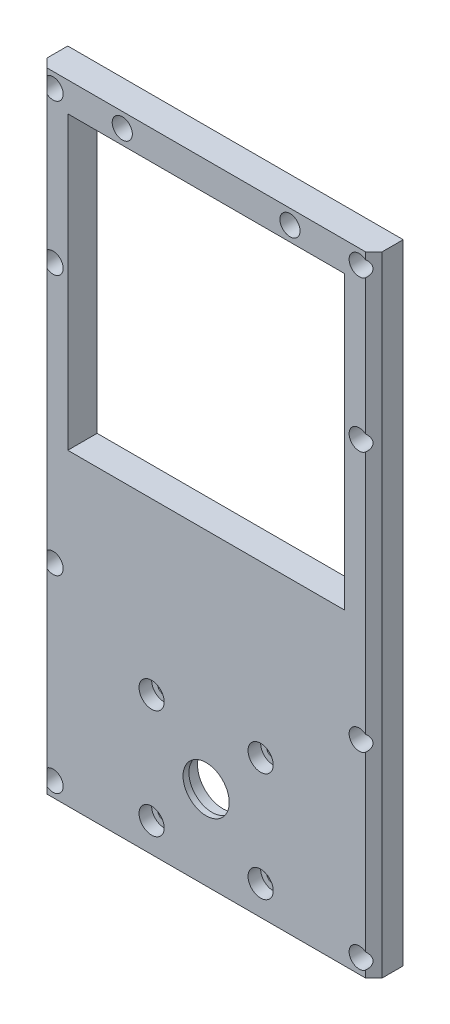
SolidWorks part; units mm, degrees
ref_plane "Front Plane" through (0, 0, 0) normal (0, 0, 1) x (1, 0, 0)
ref_plane "Top Plane" through (0, 0, 0) normal (0, 1, 0) x (1, 0, 0)
ref_plane "Right Plane" through (0, 0, 0) normal (1, 0, 0) x (0, 0, -1)
sketch "Sketch1" plane through (0, 0, 0) normal (0, 0, 1) x (1, 0, 0)
  line L1 (-40, -75) -> (40, -75)
  line L2 (-40, -75) -> (-40, 75)
  line L3 (-40, 75) -> (40, 75)
  line L4 (40, -75) -> (40, 75)
  line L5 (-40, -75) -> (40, 75) construction
  line L6 (-40, 75) -> (40, -75) construction
  line L7 (-33, -68) -> (33, -68)
  line L8 (-33, -68) -> (-33, 68)
  line L9 (-33, 68) -> (33, 68)
  line L10 (33, -68) -> (33, 68)
  line L11 (-33, -68) -> (33, 68) construction
  line L12 (-33, 68) -> (33, -68) construction
  point P0 (0, 0)
  point P6 (0, 0)
  dimension "D1" = 150
  dimension "D2" = 80
  dimension "D3" = 7
  dimension "D4" = 7
extrude "Boss-Extrude1" add sketch "Sketch1" along normal blind 7
sketch "Sketch2" plane through (0, 0, 7) normal (0, 0, 1) x (1, 0, 0)
  line L0 (33, -68) -> (33, 68) construction
  line L1 (-33, -68) -> (33, -68)
  line L2 (-33, -68) -> (-33, -32)
  line L3 (-33, -32) -> (33, -32)
  line L4 (33, -68) -> (33, -32)
  dimension "D1" = 36
extrude "Boss-Extrude2" add sketch "Sketch2" against normal up to surface (7 mm away) up to face at (0, 0, 0)
sketch "Sketch3" plane through (0, 0, 0) normal (0, 0, -1) x (-1, 0, 0)
  line L0 (0, -75) -> (0, -55) construction
  line L1 (40, -75) -> (-40, -75) construction
  circle A0 centre (0, -55) radius 5.5
  dimension "D1" = 11
  dimension "D2" = 20
extrude "Cut-Extrude1" cut sketch "Sketch3" against normal through all
sketch "Sketch4" plane through (0, 0, 0) normal (0, 0, -1) x (-1, 0, 0)
  circle A0 centre (0, -55) radius 6.05
  dimension "D1" = 12.1
extrude "Cut-Extrude2" cut sketch "Sketch4" against normal offset from surface (5.6 mm away) 1.4 up to face at (-5.5, -55, 7)
sketch "Sketch5" plane through (0, 0, 0) normal (0, 0, -1) x (-1, 0, 0)
  circle A0 centre (0, -55) radius 11
  dimension "D1" = 22
extrude "Cut-Extrude3" cut sketch "Sketch5" against normal offset from surface (3 mm away) 2.6 up to face at (-6.05, -55, 5.6)
sketch "Sketch6" plane through (0, 0, 0) normal (0, 0, -1) x (-1, 0, 0)
  line L1 (-13, -68) -> (13, -68) construction
  line L2 (-13, -68) -> (-13, -42) construction
  line L3 (-13, -42) -> (13, -42) construction
  line L4 (13, -68) -> (13, -42) construction
  line L5 (-13, -68) -> (13, -42) construction
  line L6 (-13, -42) -> (13, -68) construction
  circle A0 centre (-13, -42) radius 1.6
  circle A1 centre (13, -42) radius 1.6
  circle A2 centre (13, -68) radius 1.6
  circle A3 centre (-13, -68) radius 1.6
  point P0 (0, -55)
  dimension "D2" = 3.2
  dimension "D1" = 26
extrude "Cut-Extrude4" cut sketch "Sketch6" against normal through all
sketch "Sketch7" plane through (0, 0, 0) normal (0, 0, -1) x (-1, 0, 0)
  line L1 (-25, -74) -> (25, -74)
  line L2 (-25, -74) -> (-25, -36)
  line L3 (-25, -36) -> (25, -36)
  line L4 (25, -74) -> (25, -36)
  line L5 (-25, -74) -> (25, -36) construction
  line L6 (-25, -36) -> (25, -74) construction
  point P0 (0, -55)
  dimension "D1" = 50
  dimension "D2" = 38
extrude "Cut-Extrude5" cut sketch "Sketch7" against normal blind 1
sketch "Sketch8" plane through (0, 0, 7) normal (0, 0, 1) x (1, 0, 0)
  circle A0 centre (-13, -42) radius 3
  circle A1 centre (13, -42) radius 3
  circle A2 centre (13, -68) radius 3
  circle A3 centre (-13, -68) radius 3
  dimension "D1" = 6
extrude "Cut-Extrude6" cut sketch "Sketch8" against normal blind 3
sketch "Sketch9" plane through (0, 0, 7) normal (0, 0, 1) x (1, 0, 0)
  line L0 (-40, 75) -> (-40, -75) construction
  line L1 (-36.5, -71.5) -> (36.5, -71.5) construction
  line L2 (-36.5, -71.5) -> (-36.5, 71.5) construction
  line L3 (-36.5, 71.5) -> (36.5, 71.5) construction
  line L4 (36.5, -71.5) -> (36.5, 71.5) construction
  line L5 (-36.5, -71.5) -> (36.5, 71.5) construction
  line L6 (-36.5, 71.5) -> (36.5, -71.5) construction
  line L7 (40, 75) -> (-40, 75) construction
  circle A0 centre (-36.5, 71.5) radius 1.35
  circle A1 centre (36.5, 71.5) radius 1.35
  circle A4 centre (-36.5, -71.5) radius 1.35
  circle A5 centre (36.5, -71.5) radius 1.35
  circle A6 centre (-36.5, 35.5) radius 1.35
  circle A7 centre (36.5, 35.5) radius 1.35
  circle A8 centre (36.5, -26.5) radius 1.35
  circle A9 centre (-36.5, -26.5) radius 1.35
  point P0 (0, 0)
  dimension "D3" = 2.7
  dimension "D1" = 3.5
  dimension "D2" = 3.5
  dimension "D4" = 45
  dimension "D5" = 36
extrude "Cut-Extrude7" cut sketch "Sketch9" against normal through all
sketch "Sketch10" plane through (0, 0, 7) normal (0, 0, 1) x (1, 0, 0)
  circle A0 centre (-36.5, 71.5) radius 2.4
  circle A1 centre (36.5, 35.5) radius 2.4
  circle A2 centre (-36.5, 35.5) radius 2.4
  circle A3 centre (36.5, 71.5) radius 2.4
  circle A4 centre (-36.5, -71.5) radius 2.4
  circle A5 centre (36.5, -71.5) radius 2.4
  circle A6 centre (-36.5, -26.5) radius 2.4
  circle A7 centre (36.5, -26.5) radius 2.4
  dimension "D1" = 4.8
extrude "Cut-Extrude8" cut sketch "Sketch10" against normal blind 5
chamfer "Chamfer1" distance 2 angle 45 2 edges at (-40, 0, 7) (40, 0, 7)
sketch "Sketch11" plane through (0, 0, 7) normal (0, 0, 1) x (1, 0, 0)
  line L0 (33, -32) -> (33, 68) construction
  line L1 (-33, -32) -> (33, -32)
  line L2 (-33, -32) -> (-33, -1.5)
  line L3 (-33, -1.5) -> (33, -1.5)
  line L4 (33, -32) -> (33, -1.5)
  line L5 (-38, -75) -> (38, -75) construction
  dimension "D1" = 73.5
extrude "Boss-Extrude3" add sketch "Sketch11" against normal up to surface (7 mm away) up to face at (-35.15, -71.5, 0)
sketch "Sketch12" plane through (0, 0, 7) normal (0, 0, 1) x (1, 0, 0)
  line L0 (-36.5, 71.5) -> (36.5, 71.5) construction
  line L1 (-20, 71.5) -> (20, 71.5) construction
  circle A0 centre (-20, 71.5) radius 1.35
  circle A1 centre (20, 71.5) radius 1.35
  circle A2 centre (-36.5, 71.5) radius 1.35 construction
  point P7 (0, 71.5)
  dimension "D1" = 40
extrude "Cut-Extrude9" cut sketch "Sketch12" against normal through all
sketch "Sketch13" plane through (0, 0, 7) normal (0, 0, 1) x (1, 0, 0)
  circle A0 centre (-20, 71.5) radius 2.4
  circle A1 centre (20, 71.5) radius 2.4
  circle A2 centre (-36.5, 71.5) radius 2.4 construction
extrude "Cut-Extrude10" cut sketch "Sketch13" against normal up to surface (5 mm away) up to face at (-34.1, 71.5, 2)
